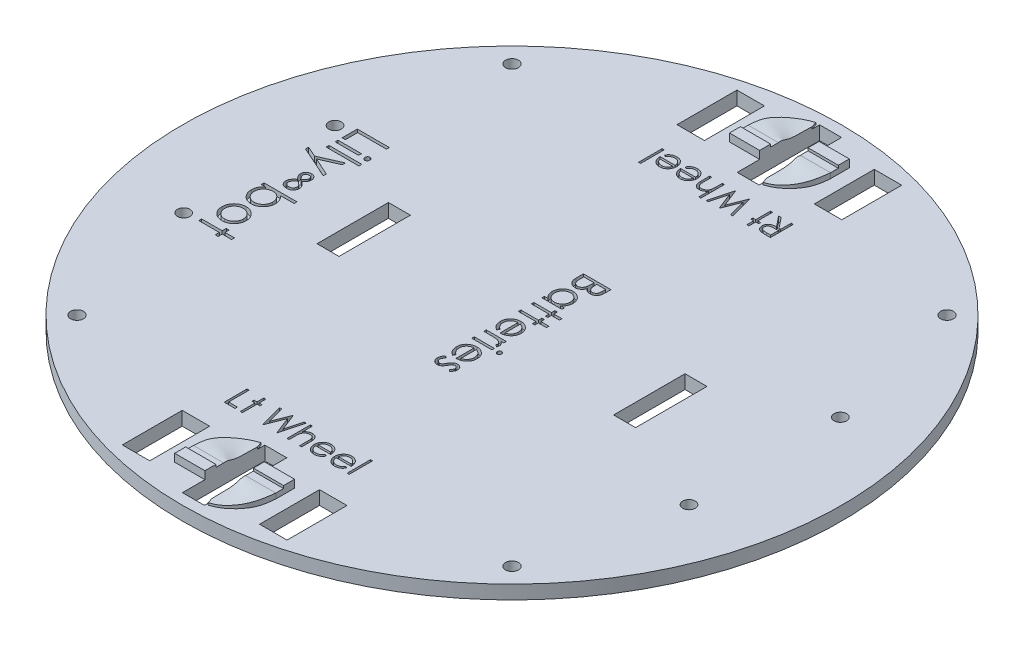
SolidWorks part; units mm, degrees
ref_plane "Front" through (0, 0, 0) normal (0, 0, 1) x (1, 0, 0)
ref_plane "Top" through (0, 0, 0) normal (0, 1, 0) x (1, 0, 0)
ref_plane "Right" through (0, 0, 0) normal (1, 0, 0) x (0, 0, -1)
sketch "Sketch1" plane through (0, 0, 0) normal (0, 1, 0) x (1, 0, 0)
  circle A0 centre (0, 0) radius 76.2
  dimension "D1" = 152.4
extrude "Boss-Extrude1" add sketch "Sketch1" along normal blind 3.175 contours A0
sketch "Sketch2" plane through (0, 3.175, 0) normal (0, 1, 0) x (1, 0, 0)
  line L1 (-2.54, -73.66) -> (2.54, -73.66)
  line L2 (-2.54, -73.66) -> (-2.54, -54.61)
  line L3 (-2.54, -54.61) -> (2.54, -54.61)
  line L4 (2.54, -73.66) -> (2.54, -54.61)
  circle A0 centre (0, 0) radius 76.2 construction
  point P4 (0, -54.61)
  dimension "D1" = 5.08
  dimension "D2" = 19.05
  dimension "D3" = 73.66
extrude "Cut-Extrude1" cut sketch "Sketch2" against normal up to next and the other way through all contours L1 L4 L3 L2
sketch "Sketch4" plane through (0, 3.175, 0) normal (0, 1, 0) x (1, 0, 0)
  line L0 (0, -64.135) -> (-2.9434, -55.0762) construction
  line L1 (-2.9434, -55.0762) -> (0, -64.135) construction
  line L2 (0, -64.135) -> (-5.5987, -56.4291) construction
  line L3 (0, -64.135) -> (-7.7059, -58.5363) construction
  line L4 (0, -64.135) -> (-9.0588, -61.1916) construction
  line L5 (0, -64.135) -> (-9.525, -64.135) construction
  line L9 (2.54, -54.61) -> (-2.54, -54.61) construction
  line L10 (2.54, -54.61) -> (2.54, -73.66) construction
  line L11 (-2.54, -54.61) -> (-2.54, -73.66) construction
  line L12 (2.54, -73.66) -> (-2.54, -73.66) construction
  circle A0 centre (0, -64.135) radius 9.525 construction
  point P16 (0, -54.61)
  point P19 (2.54, -64.135)
  dimension "D1" = 18
  dimension "D2" = 18
  dimension "D3" = 18
  dimension "D4" = 18
  dimension "D5" = 18
ref_plane "Plane1" through (-18.8488, 0, 6.1243) normal (0.9511, 0, -0.309) x (-0.309, 0, -0.9511)
ref_plane "Plane2" through (-30.498, 0, 22.1581) normal (0.809, 0, -0.5878) x (-0.5878, 0, -0.809)
ref_plane "Plane3" through (-30.498, 0, 41.9769) normal (0.5878, 0, -0.809) x (-0.809, 0, -0.5878)
ref_plane "Plane4" through (-18.8488, 0, 58.0107) normal (0.309, 0, -0.9511) x (-0.9511, 0, -0.309)
ref_plane "Plane5" through (0, 0, 64.135) normal (0, 0, -1) x (-1, 0, 0)
sketch "Sketch5" plane through (-18.8488, 0, 6.1243) normal (0.9511, 0, -0.309) x (-0.309, 0, -0.9511)
  line L0 (-51.1523, 3.175) -> (-69.2699, 3.175) construction
  line L1 (-52.7764, 3.175) -> (-51.471, 3.175)
  line L2 (-52.7764, 3.175) -> (-52.7764, 3.683)
  line L3 (-52.7764, 3.683) -> (-51.471, 3.683)
  line L4 (-51.471, 3.175) -> (-51.471, 3.683)
  dimension "D2" = 0.508
sketch "Sketch6" plane through (-30.498, 0, 22.1581) normal (0.809, 0, -0.5878) x (-0.5878, 0, -0.809)
  line L0 (-42.6874, 3.175) -> (-58.0992, 3.175) construction
  line L1 (-47.565, 3.175) -> (-42.3613, 3.175)
  line L2 (-47.565, 3.175) -> (-47.565, 3.775)
  line L3 (-47.565, 3.775) -> (-42.3613, 3.775)
  line L4 (-42.3613, 3.175) -> (-42.3613, 3.775)
  dimension "D2" = 0.6
sketch "Sketch7" plane through (-30.498, 0, 41.9769) normal (0.5878, 0, -0.809) x (-0.809, 0, -0.5878)
  line L0 (-30.044, 3.175) -> (-41.2414, 3.175) construction
  line L1 (-34.558, 3.175) -> (-28.1726, 3.175)
  line L2 (-34.558, 3.175) -> (-34.558, 4.075)
  line L3 (-34.558, 4.075) -> (-28.1726, 4.075)
  line L4 (-28.1726, 3.175) -> (-28.1726, 4.075)
  dimension "D2" = 0.9
sketch "Sketch10" plane through (-18.8488, 0, 58.0107) normal (0.309, 0, -0.9511) x (-0.9511, 0, -0.309)
  line L0 (-19.8188, 3.175) -> (-10.76, 3.175) construction
  line L1 (-17.1481, 3.175) -> (-10.2938, 3.175)
  line L2 (-17.1481, 3.175) -> (-17.1481, 4.375)
  line L3 (-17.1481, 4.375) -> (-10.2938, 4.375)
  line L4 (-10.2938, 3.175) -> (-10.2938, 4.375)
  dimension "D3" = 1.2
sketch "Sketch11" plane through (0, 0, 64.135) normal (0, 0, -1) x (-1, 0, 0)
  line L0 (0, 3.175) -> (9.525, 3.175) construction
  line L1 (2.54, 3.175) -> (9.525, 3.175)
  line L2 (2.54, 3.175) -> (2.54, 4.375)
  line L3 (2.54, 4.375) -> (9.525, 4.375)
  line L4 (9.525, 3.175) -> (9.525, 4.375)
  dimension "D3" = 1.2
loft "Loft1" add profiles "Sketch5", "Sketch6", "Sketch7", "Sketch10", "Sketch11" connector at (-2.54, 3.683, 56.3177) connector at (-2.54, 3.775, 60.639) connector at (-2.54, 4.075, 62.2896) connector at (-2.54, 4.375, 63.3097) connector at (-2.54, 4.375, 64.135)
sketch "Sketch13" plane through (-104.9799, 0, 64.135) normal (0, 0, -1) x (-1, 0, 0)
  line L6 (-95.4549, 3.175) -> (-102.4399, 3.175)
  line L7 (-95.4549, 3.175) -> (-95.4549, 4.375)
  line L8 (-95.4549, 4.375) -> (-102.4399, 4.375)
  line L9 (-102.4399, 3.175) -> (-102.4399, 4.375)
extrude "Boss-Extrude4" add sketch "Sketch13" against normal blind 1.7907
sketch "Sketch25" plane through (0, 0, 65.9257) normal (0, 0, 1) x (1, 0, 0)
  line L0 (-9.525, 4.375) -> (-2.54, 4.375) construction
  line L1 (-9.525, 3.175) -> (-2.54, 3.175)
  line L2 (-9.525, 3.175) -> (-9.525, 4.975)
  line L3 (-9.525, 4.975) -> (-2.54, 4.975)
  line L4 (-2.54, 3.175) -> (-2.54, 4.975)
  dimension "D1" = 0.6
extrude "Boss-Extrude5" add sketch "Sketch25" along normal blind 2.54
sketch "Sketch14" plane through (-2.54, 0, 0) normal (1, 0, 0) x (0, 0, -1)
  line L0 (-64.135, 3.175) -> (-64.135, 0) construction
  line L1 (-54.61, 0) -> (-73.66, 0) construction
ref_plane "Plane6" through (0, 0, 0) normal (1, 0, 0) x (0, 0, -1)
sketch "Sketch15" plane through (0, 0, 0) normal (1, 0, 0) x (0, 0, -1)
  line L0 (-64.135, 0) -> (-64.135, 3.175) construction
pattern_circular "CirPattern1" count 2 over 360 about axis through (0, 0, 64.135) along (0, 1, 0) of "Loft1", "Boss-Extrude5", "Boss-Extrude4" reverse direction yes
ref_axis "Axis1" through (0, 50, 0) along (0, -1, 0)
pattern_circular "CirPattern5" count 2 over 360 about axis through (0, 50, 0) along (0, -1, 0) of "CirPattern1", "Cut-Extrude1"
sketch "Sketch18" plane through (0, 3.175, 0) normal (0, 1, 0) x (1, 0, 0)
  line L4 (0, -76.2) -> (0, 76.2) construction
  line L5 (0, -1.7463) -> (0, 1.7463) construction
  line L6 (-76.2, 0) -> (76.2, 0) construction
  circle A8 centre (0, 0) radius 76.2 construction
sketch "Sketch19" plane through (0, 3.175, 0) normal (0, 1, 0) x (1, 0, 0)
  line L0 (-50.2894, -50.2894) -> (0, 0) construction
  line L1 (0, -76.2) -> (0, 76.2) construction
  circle A1 centre (-50.2894, -50.2894) radius 1.5
  circle A4 centre (0, 0) radius 76.2 construction
  dimension "D4" = 3
  dimension "D6" = 71.12
  dimension "D5" = 45
extrude "Cut-Extrude2" cut sketch "Sketch19" against normal through all
pattern_circular "CirPattern7" count 4 over 360 about axis through (0, 50, 0) along (0, -1, 0) of "Cut-Extrude2"
sketch "Sketch23" plane through (0, 3.175, 0) normal (0, 1, 0) x (1, 0, 0)
  line L9 (-2.54, -68.4657) -> (-2.54, -73.66) construction
  line L10 (-19.05, -57.2072) -> (-12.7, -57.2072)
  line L11 (-19.05, -57.2072) -> (-19.05, -71.0628)
  line L16 (-19.05, -71.0628) -> (-12.7, -71.0628)
  line L17 (-12.7, -57.2072) -> (-12.7, -71.0628)
  line L19 (2.54, -54.61) -> (2.54, -59.8043) construction
  line L20 (0, -50) -> (0, 50) construction
  line L21 (12.7, -57.2072) -> (12.7, -71.0628)
  line L22 (19.05, -71.0628) -> (12.7, -71.0628)
  line L23 (19.05, -57.2072) -> (19.05, -71.0628)
  line L24 (19.05, -57.2072) -> (12.7, -57.2072)
  point P8 (-2.54, -71.0628)
  point P9 (2.54, -57.2072)
  dimension "D1" = 6.35
  dimension "D2" = 10.16
extrude "Cut-Extrude6" cut sketch "Sketch23" against normal through all
pattern_circular "CirPattern8" count 2 over 360 about axis through (0, 50, 0) along (0, -1, 0) of "Cut-Extrude6"
sketch "Sketch17" plane through (0, 3.175, 0) normal (0, 1, 0) x (1, 0, 0)
  line L0 (-19.05, -45.72) -> (19.05, -45.72) construction
  point P3 (0, -45.72)
  dimension "D2" = 45.72
  dimension "D1" = 38.1
sketch "Sketch16" plane through (0, 3.175, 0) normal (0, 1, 0) x (1, 0, 0)
  line L0 (-19.05, -45.72) -> (19.05, -45.72) construction
  line L1 (0, -19.05) -> (0, 19.05) construction
  line L2 (0, -76.2) -> (0, 76.2) construction
  line L3 (-16.51, -50.7135) -> (16.51, -50.7135) construction
  line L4 (-76.2, 0) -> (76.2, 0) construction
  line L5 (-16.51, 50.6787) -> (16.51, 50.6787) construction
  line L6 (-55.1391, 20.32) -> (-55.1391, -20.32) construction
  text T0 "Lily∞bot\r\n" font "Century Gothic" height in points 28
  text T1 "Batteries"
  text T2 "Lt Wheel\r\n" font "Century Gothic" height in points 20
  text T3 "Rt Wheel" font "Century Gothic" height in points 20
  point P4 (0, -50.7135)
  point P10 (0, 0)
  point P15 (0, 50.6787)
  point P17 (-55.1391, 0)
  dimension "D1" = 38.1
  dimension "D2" = 33.02
  dimension "D3" = 40.64
extrude "Cut-Extrude4" cut sketch "Sketch16" along a picked direction on the side against the normal blind 1.27
sketch "Sketch26" plane through (0, 3.175, 0) normal (0, 1, 0) x (1, 0, 0)
  line L0 (-76.2, 0) -> (76.2, 0) construction
  line L1 (-36.83, 8.255) -> (-31.75, 8.255)
  line L2 (-36.83, 8.255) -> (-36.83, -8.255)
  line L3 (-36.83, -8.255) -> (-31.75, -8.255)
  line L4 (-31.75, 8.255) -> (-31.75, -8.255)
  line L5 (0, -76.2) -> (0, 76.2) construction
  point P4 (-36.83, 0)
  dimension "D1" = 16.51
  dimension "D2" = 5.08
  dimension "D3" = 31.75
extrude "Cut-Extrude7" cut sketch "Sketch26" against normal through all
mirror "Mirror1" about plane through (0, 0, 0) normal (1, 0, 0) of "Cut-Extrude7"
sketch "Sketch27" plane through (0, 0, 0) normal (0, -1, 0) x (-1, 0, 0)
  line L3 (76.2, 0) -> (-76.2, 0) construction
  line L4 (0, -76.2) -> (0, 76.2) construction
  circle A0 centre (-58.42, 17.5) radius 1.45
  dimension "D2" = 58.42
  dimension "D3" = 2.9
  dimension "D1" = 17.5
extrude "Cut-Extrude8" cut sketch "Sketch27" against normal through all both and the other way through all
mirror "Mirror2" about plane through (0, 0, 0) normal (1, 0, 0) of "Cut-Extrude8"
mirror "Mirror3" about plane through (0, 0, 0) normal (0, 0, 1) of "Mirror2"
sketch "Sketch28" plane through (0, 0, 0) normal (0, -1, 0) x (-1, 0, 0)
  line L0 (52.1625, -19.05) -> (52.1625, 19.05) construction
  line L2 (-52.2165, -22.225) -> (-52.2165, 22.225) construction
  text T0 "Ft Caster"
  text T1 "Bk Caster"
  dimension "D1" = 38.1
  dimension "D4" = 44.45
extrude "Cut-Extrude10" cut sketch "Sketch28" against normal blind 1.27
